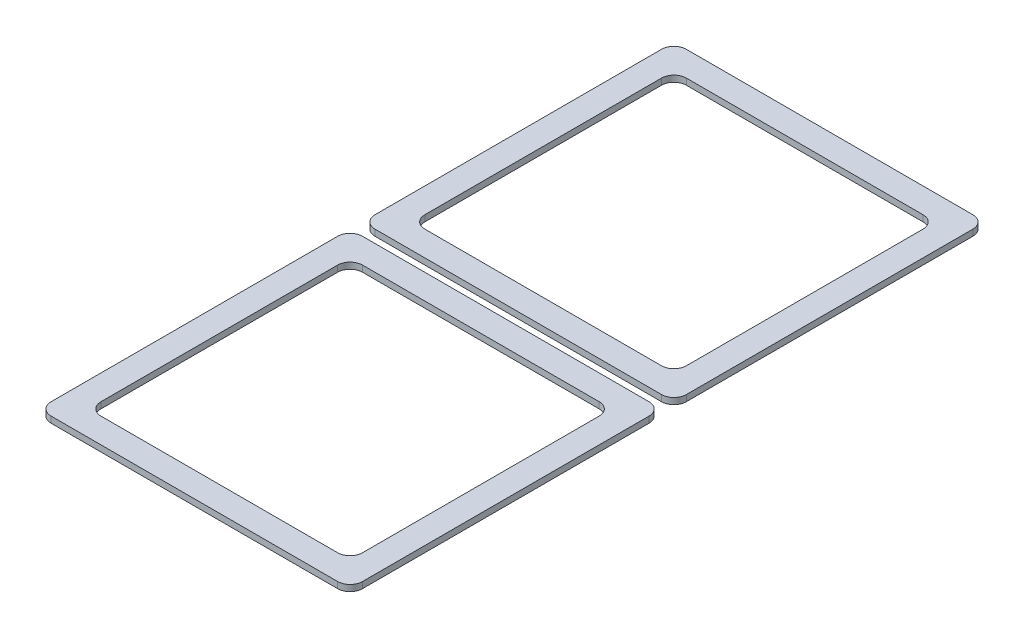
SolidWorks part; units mm, degrees
note: '?' marks a value the reader was unsure of.
ref_plane "前视基准面" through (0, 0, 0) normal (0, 0, 1) x (1, 0, 0)
ref_plane "上视基准面" through (0, 0, 0) normal (0, 1, 0) x (1, 0, 0)
ref_plane "右视基准面" through (0, 0, 0) normal (1, 0, 0) x (0, 0, -1)
sketch "草图1" plane through (0, 0, 0) normal (0, 1, 0) x (1, 0, 0)
  line L0 (-9.5, 23.5) -> (9.5, 23.5)
  line L1 (-11.5, 0.5) -> (11.5, 0.5)
  line L2 (-12.5, 1.5) -> (-12.5, 24.5)
  line L3 (-11.5, 25.5) -> (11.5, 25.5)
  line L4 (12.5, 1.5) -> (12.5, 24.5)
  line L5 (-12.5, 0.5) -> (12.5, 25.5) construction
  line L6 (-12.5, 25.5) -> (12.5, 0.5) construction
  line L7 (10.5, 3.5) -> (10.5, 22.5)
  line L8 (-9.5, 2.5) -> (9.5, 2.5)
  line L9 (-10.5, 3.5) -> (-10.5, 22.5)
  line L10 (-10.5, 2.5) -> (-10.5, 23.5) construction
  line L11 (-10.5, 23.5) -> (10.5, 23.5) construction
  line L12 (-12.5, 0.5) -> (-12.5, 25.5) construction
  line L13 (-12.5, 25.5) -> (12.5, 25.5) construction
  line L14 (12.5, 0.5) -> (12.5, 25.5) construction
  line L15 (10.5, 2.5) -> (10.5, 23.5) construction
  line L16 (-12.5, 0.5) -> (12.5, 0.5) construction
  line L17 (-10.5, 2.5) -> (10.5, 2.5) construction
  arc A0 (-10.5, 22.5) -> (-9.5, 23.5) centre (-9.5, 22.5) cw
  arc A1 (-12.5, 24.5) -> (-11.5, 25.5) centre (-11.5, 24.5) cw
  arc A2 (12.5, 24.5) -> (11.5, 25.5) centre (11.5, 24.5) ccw
  arc A3 (10.5, 22.5) -> (9.5, 23.5) centre (9.5, 22.5) ccw
  arc A4 (-11.5, 0.5) -> (-12.5, 1.5) centre (-11.5, 1.5) cw
  arc A5 (-9.5, 2.5) -> (-10.5, 3.5) centre (-9.5, 3.5) cw
  arc A6 (9.5, 2.5) -> (10.5, 3.5) centre (9.5, 3.5) ccw
  arc A7 (11.5, 0.5) -> (12.5, 1.5) centre (11.5, 1.5) ccw
  point P0 (0, 13)
  dimension "D4" = 1
  dimension "D5" = 1
  dimension "D6" = 1
  dimension "D7" = 1
  dimension "D1" = 25
  dimension "D2" = 13
  dimension "D3" = 2
extrude "凸台-拉伸1" add sketch "草图1" along normal blind 0.5
ref_axis "基准轴2" through (0, 0, 0) along (1, 0, 0)?
sketch "草图2" plane through (0, 0, 0) normal (1, 0, 0) x (0, 0, -1)
  line L1 (23.5, 0.5) -> (25.5, 0.5)
  line L2 (23.5, 0.5) -> (23.5, 0)
  line L3 (23.5, 0) -> (25.5, 0)
  line L4 (25.5, 0.5) -> (25.5, 0)
surface "曲面-基准面1" sketch "草图2"
ref_axis "基准轴1" through (0, 0, 0) along (0, 1, 0)?
pattern_circular "阵列(圆周)1" count 2 every 180 about axis through (0, 0, 0) along (0, 1, 0) of bodies 106 107
